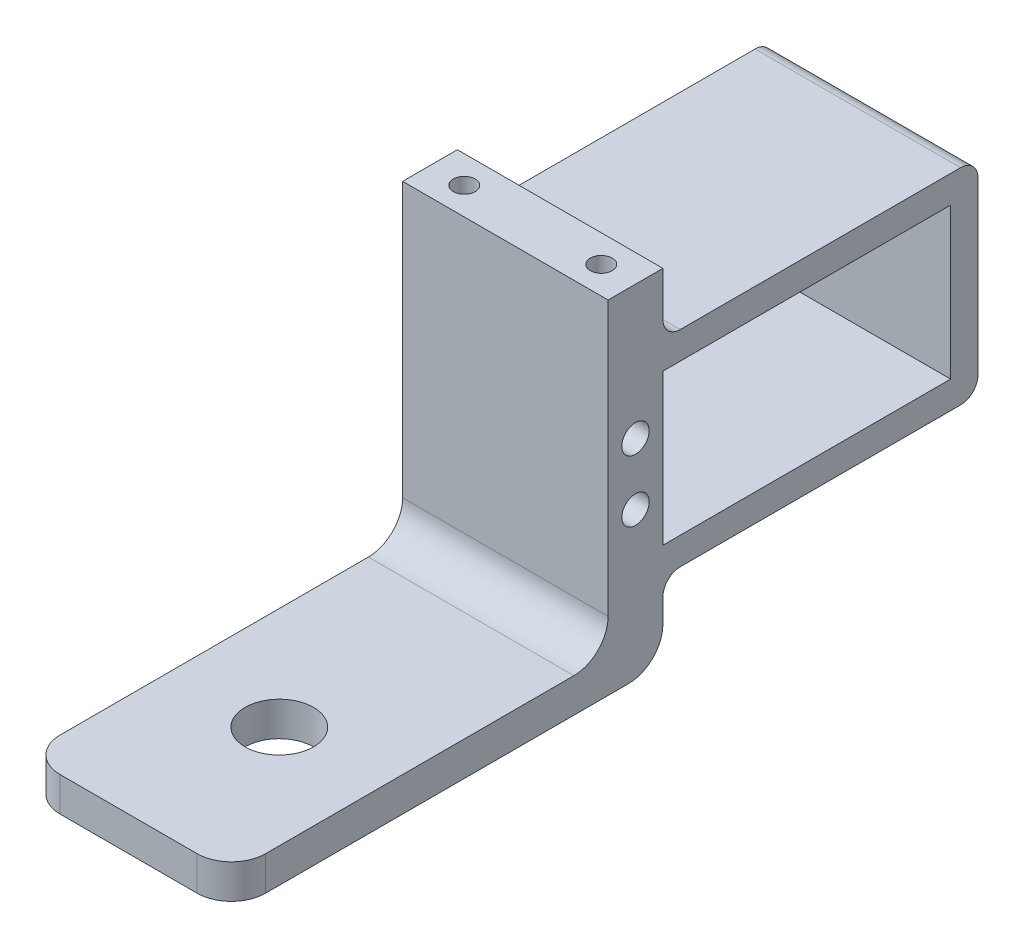
SolidWorks part; units mm, degrees
ref_plane "Front Plane" through (0, 0, 0) normal (0, 0, 1) x (1, 0, 0)
ref_plane "Top Plane" through (0, 0, 0) normal (0, 1, 0) x (1, 0, 0)
ref_plane "Right Plane" through (0, 0, 0) normal (1, 0, 0) x (0, 0, -1)
sketch "Sketch1" plane through (0, 0, 0) normal (1, 0, 0) x (0, 0, -1)
  line L1 (0, 0) -> (63, 0)
  line L2 (0, 0) -> (0, 5)
  line L3 (0, 5) -> (63, 5)
  line L4 (63, 0) -> (63, 5)
  dimension "D1" = 5
  dimension "D2" = 63
extrude "Boss-Extrude1" add sketch "Sketch1" along normal blind 30 contours L3 L4 L1 L2
sketch "Sketch2" plane through (0, 5, 0) normal (0, 1, 0) x (1, 0, 0)
  line L0 (30, 0) -> (30, 63) construction
  line L1 (0, 63) -> (30, 63)
  line L2 (0, 63) -> (0, 55)
  line L3 (0, 55) -> (30, 55)
  line L4 (30, 63) -> (30, 55)
  dimension "D1" = 8
extrude "Boss-Extrude2" add sketch "Sketch2" along normal blind 45
sketch "Sketch3" plane through (0, 5, 0) normal (0, 1, 0) x (1, 0, 0)
  line L0 (30, 0) -> (0, 0) construction
  circle A0 centre (15, 22) radius 5
  point P4 (15, 0)
  dimension "D2" = 10
  dimension "D1" = 22
extrude "Cut-Extrude1" cut sketch "Sketch3" against normal through all
sketch "Sketch5" plane through (0, 50, 0) normal (0, 1, 0) x (1, 0, 0)
  line L0 (0, 63) -> (0, 55) construction
  line L1 (30, 55) -> (30, 63) construction
  circle A0 centre (5, 59) radius 1.6
  circle A1 centre (25, 59) radius 1.6
  point P5 (0, 59)
  dimension "D1" = 3.2
  dimension "D3" = 5
  dimension "D2" = 5
extrude "Cut-Extrude3" cut sketch "Sketch5" against normal blind 14
fillet "Fillet1" radius 5 4 edges at (15, 0, -63) (15, 5, -55) (30, 2.5, 0) (0, 2.5, 0)
sketch "Sketch6" plane through (30, 0, 0) normal (1, 0, 0) x (0, 0, -1)
  line L0 (63, 5) -> (63, 50) construction
  line L1 (63, 37) -> (105, 37)
  line L2 (63, 37) -> (63, 15)
  line L3 (63, 15) -> (105, 15)
  line L4 (105, 37) -> (105, 15)
  line L5 (5, 0) -> (58, 0) construction
  line L6 (63, 41) -> (109, 41)
  line L7 (63, 41) -> (63, 11)
  line L8 (63, 11) -> (109, 11)
  line L9 (109, 41) -> (109, 11)
  line M11 (63, 5) -> (63, 50)
  dimension "D1" = 4
  dimension "D2" = 4
  dimension "D3" = 4
  dimension "D4" = 22
  dimension "D5" = 42
  dimension "D6" = 15
extrude "Boss-Extrude3" add sketch "Sketch6" against normal up to surface (30 mm away) contours L9 L6 L1 L4 L3 L8 M11 region at (30, 39, -63.5492) up to face at (0, 15.3661, -44.5089)
sketch "Sketch7" plane through (30, 0, 0) normal (1, 0, 0) x (0, 0, -1)
  line L0 (63, 15) -> (63, 37) construction
  line L1 (59, 30.5) -> (59, 21.5)
  circle A0 centre (59, 30.5) radius 2
  circle A1 centre (59, 21.5) radius 2
  point P4 (59, 26)
  point P5 (0, 0)
  point P8 (63, 26)
  dimension "D1" = 4
  dimension "D2" = 9
  dimension "D3" = 4
extrude "Cut-Extrude4" cut sketch "Sketch7" against normal blind 7.62 contours A0 | A1 region at (30, 22.8742, -60.3742) region at (30, 31.8742, -57.6258)
fillet "Fillet2" radius 2.54 4 edges at (15, 11, -109) (15, 11, -63) (15, 41, -63) (15, 41, -109)
